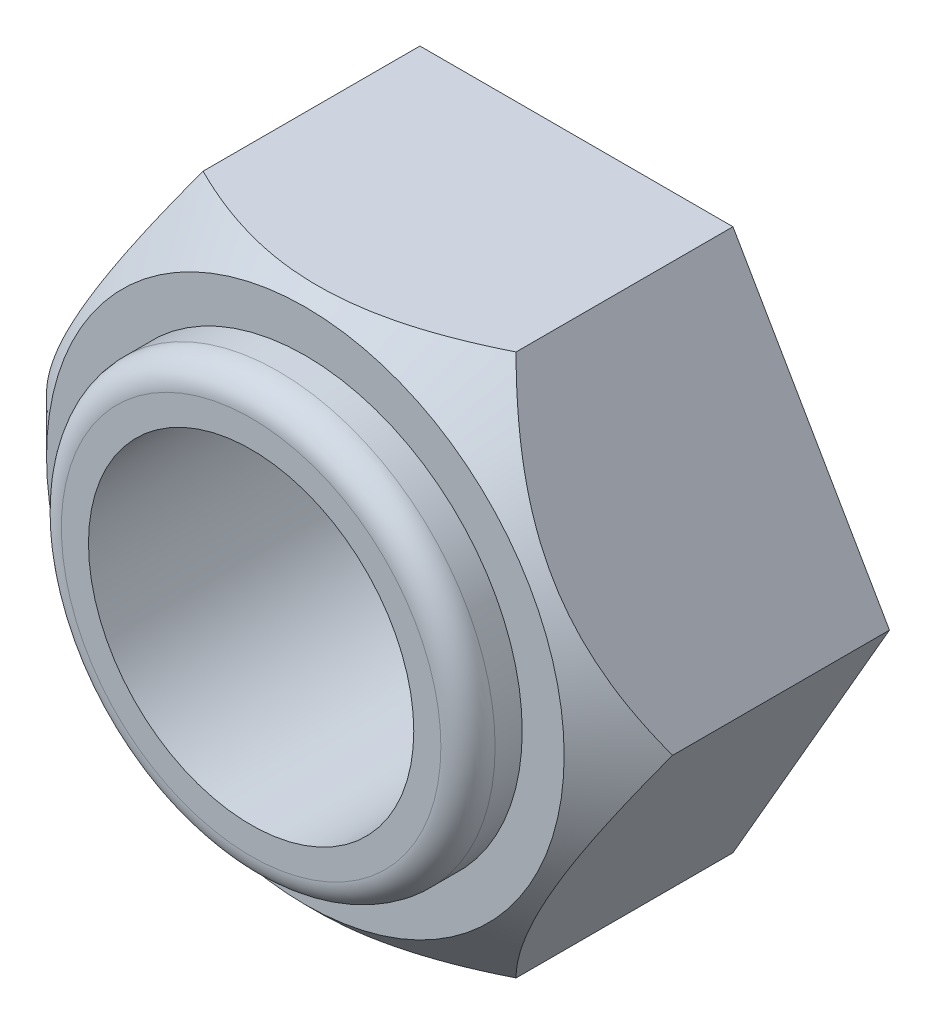
SolidWorks part; units mm, degrees
material "AISI 304"
ref_plane "前视基准面" through (0, 0, 0) normal (0, 0, 1) x (1, 0, 0)
ref_plane "上视基准面" through (0, 0, 0) normal (0, 1, 0) x (1, 0, 0)
ref_plane "右视基准面" through (0, 0, 0) normal (1, 0, 0) x (0, 0, -1)
other "Configuration Table"
sketch "草图1" plane through (0, 0, 0) normal (0, 0, 1) x (1, 0, 0)
  line L1 (5.7735, 0) -> (2.8868, 5)
  line L2 (2.8868, 5) -> (-2.8868, 5)
  line L3 (-2.8868, 5) -> (-5.7735, 0)
  line L4 (-5.7735, 0) -> (-2.8868, -5)
  line L5 (-2.8868, -5) -> (2.8868, -5)
  line L6 (2.8868, -5) -> (5.7735, 0)
  circle A0 centre (0, 0) radius 5 construction
extrude "凸台-拉伸1" add sketch "草图1" along normal blind 5
sketch "草图2" plane through (0, 0, 5) normal (0, 0, 1) x (1, 0, 0)
  circle A0 centre (0, 0) radius 4
  circle A1 centre (0, 0) radius 3
  dimension "D1" = 8
  dimension "D2" = 6
extrude "凸台-拉伸2" add sketch "草图2" along normal blind 1 contours A0
extrude "切除-拉伸1" cut sketch "草图2<3>" against normal mid plane 11 contours A1
sketch "草图2<3>" plane through (0, 0, 5) normal (0, 0, 1) x (1, 0, 0) same geometry as "草图2"
sketch "草图3" plane through (0, 0, 0) normal (0, 1, 0) x (1, 0, 0)
  line L0 (-5.7735, -5) -> (-5.7735, -4)
  line L1 (-5.7735, -5) -> (-5.7735, 0) construction
  line L2 (-5.7735, -4) -> (-4.7735, -5)
  line L3 (-2.8868, -5) -> (-5.7735, -5) construction
  line L4 (-4.7735, -5) -> (-5.7735, -5)
  line L5 (0, 0) -> (0, 50000) construction
  dimension "D1" = 1
  dimension "D2" = 1
revolve "切除-旋转1" cut sketch "草图3" angle 360 about L5
fillet "圆角3" radius 0.5 1 edges at (4, 0, 6)
